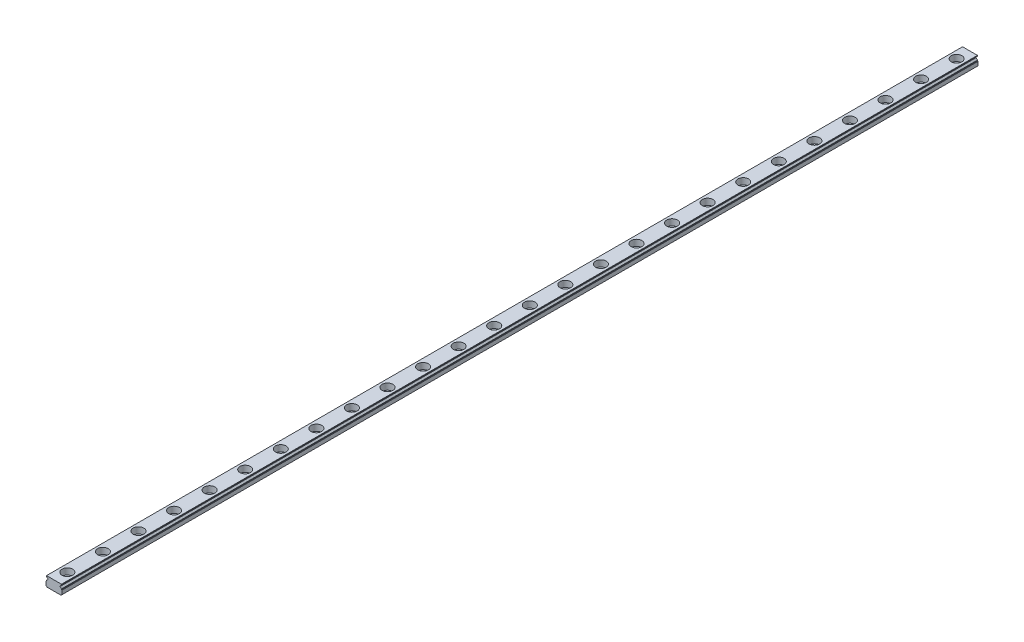
SolidWorks part; units mm, degrees
material "Chrome Stainless Steel"
ref_plane "Front Plane" through (0, 0, 0) normal (0, 0, 1) x (1, 0, 0)
ref_plane "Top Plane" through (0, 0, 0) normal (0, 1, 0) x (1, 0, 0)
ref_plane "Right Plane" through (0, 0, 0) normal (1, 0, 0) x (0, 0, -1)
sketch "Sketch1" plane through (0, 0, 0) normal (0, 0, 1) x (1, 0, 0)
  line L1 (-4.5, 0) -> (4.5, 0)
  line L2 (-4.5, 0) -> (-4.5, 5.5)
  line L3 (-4.5, 5.5) -> (4.5, 5.5)
  line L4 (4.5, 0) -> (4.5, 5.5)
  line L5 (-4.5, 0) -> (4.5, 5.5) construction
  line L6 (-4.5, 5.5) -> (4.5, 0) construction
  point P0 (0, 2.75)
  point P6 (0, 0)
  dimension "D1" = 5.5
  dimension "D2" = 9
extrude "Extrude1" add sketch "Sketch1" along normal mid plane 515
sketch "Sketch2" plane through (0, 5.5, 0) normal (0, 1, 0) x (1, 0, 0)
  line L0 (4.5, -257.5) -> (-4.5, -257.5) construction
  circle A0 centre (0, -250) radius 3
  circle A1 centre (0, -250) radius 1.75
  dimension "D1" = 6
  dimension "D2" = 3.5
  dimension "D3" = 7.5
extrude "Extrude2" cut sketch "Sketch2" against normal blind 3.5
extrude "Extrude5" cut sketch "Sketch2<3>" against normal through all contours A1 region at (0, 5.5, 250)
sketch "Sketch2<3>" plane through (0, 5.5, 0) normal (0, 1, 0) x (1, 0, 0) same geometry as "Sketch2"
pattern_linear "LPattern1" count 26 spacing 20 along (0, 0, -1) of "Extrude5", "Extrude2"
sketch "Sketch3" plane through (0, 0, 257.5) normal (0, 0, 1) x (1, 0, 0)
  line L0 (-4.2, 5.0417) -> (-3.4333, 4.275)
  line L1 (-4.5, 5.5) -> (-4.2, 5.5)
  line L2 (-4.5, 5.5) -> (-4.5, 2.75)
  line L3 (-4.5, 2.75) -> (-4.2, 2.75)
  line L4 (-4.2, 5.5) -> (-4.2, 5.0417)
  line L5 (-3.4333, 3.975) -> (-4.2, 3.2083)
  line L6 (-4.2, 3.2083) -> (-4.2, 2.75)
  line L7 (0, 5.5) -> (0, 0) construction
  line L8 (4.5, 5.5) -> (-4.5, 5.5) construction
  line L9 (-4.5, 0) -> (4.5, 0) construction
  line L10 (-3.4333, 4.275) -> (-3.2833, 4.275)
  line L11 (-3.2833, 4.275) -> (-3.2833, 3.975)
  line L12 (-3.2833, 3.975) -> (-3.4333, 3.975)
  line L13 (-3.4333, 4.275) -> (-3.2833, 4.125) construction
  line L14 (-3.2833, 4.125) -> (-3.4333, 3.975) construction
  line L15 (3.2833, 4.125) -> (3.4333, 3.975) construction
  line L16 (3.4333, 4.275) -> (3.2833, 4.125) construction
  line L17 (3.2833, 3.975) -> (3.4333, 3.975)
  line L18 (3.2833, 4.275) -> (3.2833, 3.975)
  line L19 (3.4333, 4.275) -> (3.2833, 4.275)
  line L20 (4.2, 3.2083) -> (4.2, 2.75)
  line L21 (3.4333, 3.975) -> (4.2, 3.2083)
  line L22 (4.2, 5.5) -> (4.2, 5.0417)
  line L23 (4.2, 2.75) -> (4.5, 2.75)
  line L24 (4.5, 5.5) -> (4.5, 2.75)
  line L25 (4.5, 5.5) -> (4.2, 5.5)
  line L26 (4.2, 5.0417) -> (3.4333, 4.275)
  line L27 (4.5, 0) -> (4.5, 5.5) construction
  point P30 (0, 2.75)
  dimension "D1" = 1.8333
  dimension "D2" = 0.3
  dimension "D3" = 0.3
extrude "Extrude6" cut sketch "Sketch3" against normal through all
chamfer "Chamfer1" distance 0.55 angle 45 2 edges at (-4.5, 0, 0) (4.5, 0, 0)
sketch "Sketch4" plane through (0, 0, 257.5) normal (0, 0, 1) x (1, 0, 0)
  line L0 (-4.2, 4.275) -> (4.2, 4.275) construction
  line L1 (4.2, 4.275) -> (4.2, 5.5) construction
  line L2 (4.2, 5.5) -> (-4.2, 5.5) construction
  line L3 (-4.2, 5.5) -> (-4.2, 4.275) construction
  line L4 (-3.2833, 4.275) -> (-3.2833, 2.75) construction
  line L5 (-3.2833, 2.75) -> (3.2833, 2.75) construction
  line L6 (3.2833, 2.75) -> (3.2833, 4.275) construction
  line L7 (3.2833, 4.275) -> (-3.2833, 4.275) construction
  line L8 (-4.5, 2.75) -> (4.5, 2.75) construction
  line L9 (4.5, 2.75) -> (4.5, 0) construction
  line L10 (4.5, 0) -> (-4.5, 0) construction
  line L11 (-4.5, 0) -> (-4.5, 2.75) construction
ref_plane "Plane1" through (0, 0, 257.5) normal (0, 0, 1) x (1, 0, 0)
ref_plane "Plane2" through (0, 0, -257.5) normal (0, 0, -1) x (-1, 0, 0)
equation "\"D1@Sketch3\" = \"D1@Sketch1\"/3"
equation "\"D2@Sketch3\" = \"D2@Sketch1\"/30"
equation "\"D3@Sketch3\" = \"D2@Sketch1\"/30"
